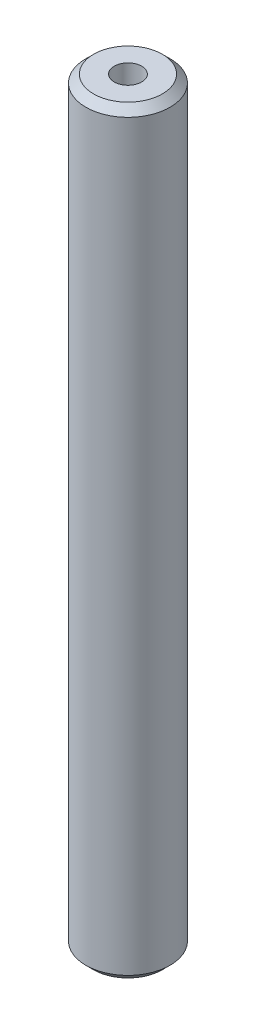
SolidWorks part; units mm, degrees
ref_plane "Front Plane" through (0, 0, 0) normal (0, 0, 1) x (1, 0, 0)
ref_plane "Top Plane" through (0, 0, 0) normal (0, 1, 0) x (1, 0, 0)
ref_plane "Right Plane" through (0, 0, 0) normal (1, 0, 0) x (0, 0, -1)
sketch "Sketch1" plane through (0, 0, 0) normal (0, 1, 0) x (1, 0, 0)
  circle A0 centre (0, 0) radius 12.5
  dimension "SHAFT_OD" = 25
extrude "Boss-Extrude1" add sketch "Sketch1" along normal blind 225.2392
sketch "Sketch2" plane through (0, 0, 0) normal (0, 1, 0) x (1, 0, 0)
  circle A0 centre (0, 0) radius 4.0779
  dimension "BORE_D" = 8.1559
extrude "Cut-Extrude1" cut sketch "Sketch2" along normal through all
chamfer "Chamfer1" distance 2.2861 angle 45 2 edges at (0, 225.2392, 12.5) (0, 0, 12.5)
